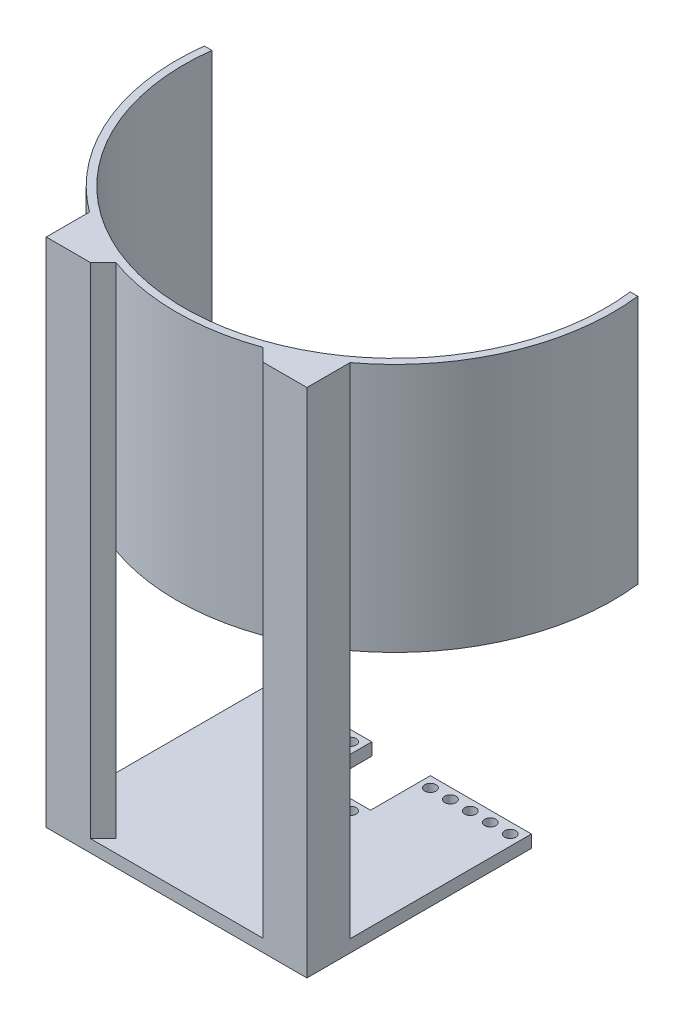
SolidWorks part; units mm, degrees
ref_plane "前视基准面" through (0, 0, 0) normal (0, 0, 1) x (1, 0, 0)
ref_plane "上视基准面" through (0, 0, 0) normal (0, 1, 0) x (1, 0, 0)
ref_plane "右视基准面" through (0, 0, 0) normal (1, 0, 0) x (0, 0, -1)
sketch "草图2" plane through (0, 0, 0) normal (0, 1, 0) x (1, 0, 0)
  line L0 (-48, 40.75) -> (-40, 40.75) construction
  line L1 (-52.25, 45) -> (52.25, 45)
  line L2 (-52.25, 45) -> (-52.25, -45)
  line L3 (-52.25, -45) -> (52.25, -45)
  line L4 (52.25, 45) -> (52.25, -45)
  line L5 (-52.25, 45) -> (52.25, -45) construction
  line L6 (-52.25, -45) -> (52.25, 45) construction
  line L7 (0, 45) -> (0, -45) construction
  line L9 (-11.75, 21) -> (11.75, 21)
  line L10 (-11.75, 21) -> (-11.75, 45)
  line L11 (-11.75, 45) -> (11.75, 45)
  line L12 (11.75, 21) -> (11.75, 45)
  line L13 (-11.75, 21) -> (11.75, 45) construction
  line L14 (-11.75, 45) -> (11.75, 21) construction
  circle A0 centre (-48, 40.75) radius 2.25
  circle A1 centre (-40, 40.75) radius 2.25
  circle A2 centre (-32, 40.75) radius 2.25
  circle A3 centre (-24, 40.75) radius 2.25
  circle A4 centre (-16, 40.75) radius 2.25
  circle A5 centre (48, 40.75) radius 2.25
  circle A6 centre (40, 40.75) radius 2.25
  circle A7 centre (32, 40.75) radius 2.25
  circle A8 centre (24, 40.75) radius 2.25
  circle A9 centre (16, 40.75) radius 2.25
  circle A10 centre (-8, 16.75) radius 2.25
  circle A11 centre (0, 16.75) radius 2.25
  circle A13 centre (8, 16.75) radius 2.25
  point P0 (0, 0)
  point P20 (0, 33)
  dimension "D3" = 4.5
  dimension "D4" = 4.25
  dimension "D10" = 4.5
  dimension "D11" = 24
  dimension "D12" = 4.5
  dimension "D13" = 8
  dimension "D1" = 104.5
  dimension "D2" = 90
  dimension "D5" = 4.25
  dimension "D7" = 8
  dimension "D8" = 4.25
  dimension "D9" = 4.25
  dimension "D6" = 5
extrude "凸台-拉伸1" add sketch "草图2" along normal blind 5 contours L12 L9 L10 L1 L2 L3 L4 A8 A6 A0 A1 A2 A3 A4 A5 A7 A9 region at (0, 0, 2.9988)
sketch "草图7" plane through (0, 5, 5) normal (0, 1, 0) x (1, 0, 0)
  line L0 (-52.25, -22.3223) -> (-52.25, -40)
  line L1 (-34.5723, -40) -> (-29.4628, -34.8905)
  line L2 (-52.25, -40) -> (52.25, -40) construction
  line L3 (-52.25, -40) -> (-34.5723, -40)
  line L4 (-50.9015, -23.6708) -> (-52.25, -22.3223)
  line L5 (34.5723, -40) -> (29.4628, -34.8905)
  line L9 (-86.8677, 58) -> (-83.8451, 58)
  line L10 (83.8451, 58) -> (86.8677, 58)
  line L11 (-52.25, 50) -> (-52.25, -40) construction
  line L12 (-34.5723, -40) -> (-50.9015, -23.6708) construction
  line L13 (34.5723, -40) -> (50.9015, -23.6708) construction
  line L15 (0, 2.25) -> (0, 7.75) construction
  line L16 (52.25, -40) -> (34.5723, -40)
  line L17 (52.25, -22.3223) -> (52.25, -40)
  line L18 (50.9015, -23.6708) -> (52.25, -22.3223)
  line L20 (-52.25, 50) -> (-11.75, 50) construction
  arc A0 (-86.8677, 58) -> (86.8677, 58) centre (0, 47.5) ccw
  arc A1 (-83.8451, 58) -> (83.8451, 58) centre (0, 47.5) ccw
  arc A2 (86.8677, 58) -> (-86.8677, 58) centre (0, 47.5) ccw construction
  arc A3 (83.8451, 58) -> (-83.8451, 58) centre (0, 47.5) ccw construction
  line M36 (-52.25, -40) -> (52.25, -40)
  line M37 (52.25, -40) -> (52.25, 50)
  dimension "D1" = 175
  dimension "D2" = 3
  dimension "D3" = 45
  dimension "D4" = 8
  dimension "D5" = 25
extrude "凸台-拉伸5" add sketch "草图7" along normal blind 100 contours A0 L0 L4 M36 | A0 L18 M36 M37 region at (-43.7412, 5, 38.9289) region at (43.7412, 5, 38.9289)
extrude "凸台-拉伸7" add sketch "草图7<5>" along normal blind 100 from surface contours A0 L0 L1 M36 | A0 L5 M36 M37 | A1 L10 A0 L9 region at (-43.7412, 5, 38.9289) region at (43.7412, 5, 38.9289) starting at face at (-42.2471, 105, 39.6059)
sketch "草图7<5>" plane through (0, 5, 5) normal (0, 1, 0) x (1, 0, 0) same geometry as "草图7"
